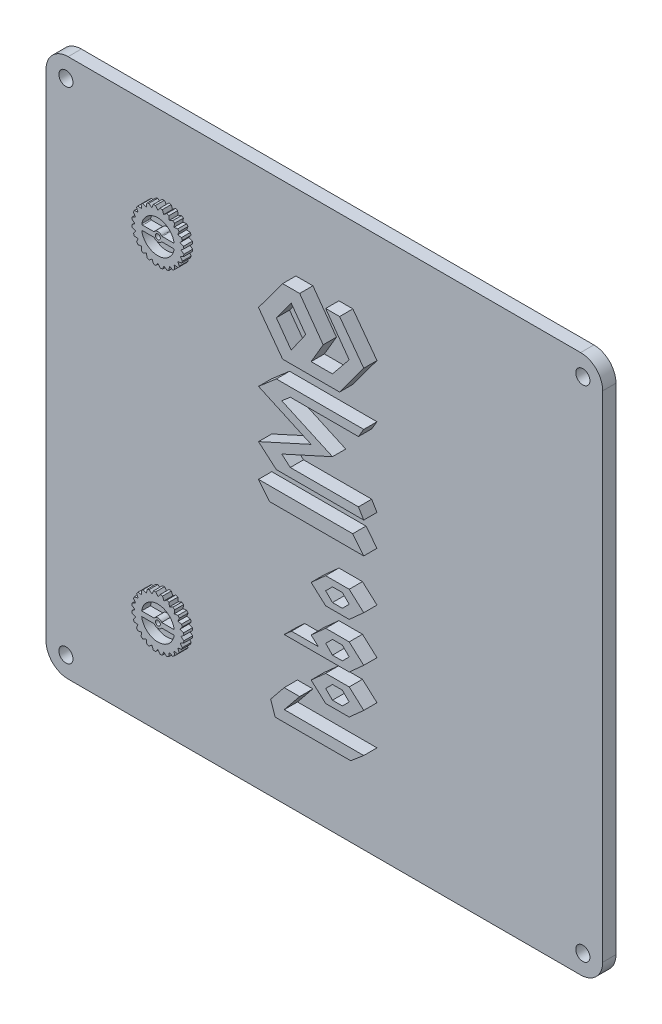
SolidWorks part; units mm, degrees
ref_plane "Front Plane" through (0, 0, 0) normal (0, 0, 1) x (1, 0, 0)
ref_plane "Top Plane" through (0, 0, 0) normal (0, 1, 0) x (1, 0, 0)
ref_plane "Right Plane" through (0, 0, 0) normal (1, 0, 0) x (0, 0, -1)
sketch "Sketch1" plane through (0, 0, 0) normal (0, 0, 1) x (1, 0, 0)
  line L1 (63, 61) -> (-63, 61)
  line L2 (63, 61) -> (63, -61)
  line L3 (63, -61) -> (-63, -61)
  line L4 (-63, 61) -> (-63, -61)
  line L5 (63, 61) -> (-63, -61) construction
  line L6 (63, -61) -> (-63, 61) construction
  point P0 (0, 0)
  dimension "D1" = 126
  dimension "D2" = 122
extrude "Boss-Extrude1" add sketch "Sketch1" along normal blind 3
sketch "Esboço8" plane through (0, 0, 3) normal (0, 0, 1) x (1, 0, 0)
  line L9 (-8.1446, -42.0239) -> (8.9552, -42.0239)
  line L15 (-6.0773, -39.5239) -> (-2.5948, -35.2227)
  line L36 (3.2914, 43.791) -> (6.4479, 43.791)
  line L47 (11.9079, -39.5239) -> (-6.0773, -39.5239)
  line L51 (11.9079, -30.6806) -> (8.6165, -27.7268)
  line L52 (3.2914, -27.7268) -> (0, -30.6806)
  line L53 (0, -30.6806) -> (3.2914, -33.6344)
  line L54 (8.6165, -33.6344) -> (11.9079, -30.6806)
  line L55 (0, -30.6806) -> (11.9079, -30.6806) construction
  line L56 (4.8336, -32.2228) -> (3.2914, -30.6806)
  line L57 (3.2914, -30.6806) -> (4.8336, -29.1384)
  line L58 (7.0744, -29.1384) -> (8.6165, -30.6806)
  line L59 (8.6165, -30.6806) -> (7.0744, -32.2228)
  line L68 (3.2914, -27.7268) -> (8.6165, -27.7268)
  line L69 (3.2914, -33.6344) -> (8.6165, -33.6344)
  line L70 (4.8336, -29.1384) -> (7.0744, -29.1384)
  line L71 (4.8336, -32.2228) -> (7.0744, -32.2228)
  line L72 (3.2914, -24.8048) -> (8.6165, -24.8048)
  line L73 (11.9079, -21.851) -> (8.6165, -24.8048)
  line L74 (8.6165, -18.8972) -> (11.9079, -21.851)
  line L75 (3.2914, -18.8972) -> (8.6165, -18.8972)
  line L76 (0, -21.851) -> (3.2914, -18.8972)
  line L77 (1.6457, -23.3279) -> (0, -21.851)
  line L78 (4.8336, -23.3932) -> (7.0744, -23.3932)
  line L79 (7.0744, -23.3932) -> (8.6165, -21.851)
  line L80 (8.6165, -21.851) -> (7.0744, -20.3088)
  line L81 (4.8336, -20.3088) -> (7.0744, -20.3088)
  line L82 (4.8336, -20.3088) -> (3.2914, -21.851)
  line L83 (3.2914, -21.851) -> (4.8336, -23.3932)
  line L84 (3.2914, -24.8048) -> (-6.0773, -24.8048)
  line L85 (-6.0773, -24.8048) -> (-4.4316, -23.3279)
  line L86 (-4.4316, -23.3279) -> (1.6457, -23.3279)
  line L87 (-2.5948, -35.2227) -> (-6.0948, -35.2227)
  line L94 (3.2914, -14.4937) -> (8.6165, -14.4937)
  line L95 (8.6165, -14.4937) -> (11.9079, -11.5399)
  line L96 (11.9079, -11.5399) -> (8.6165, -8.5862)
  line L97 (3.2914, -8.5862) -> (8.6165, -8.5862)
  line L98 (3.2914, -8.5862) -> (0, -11.5399)
  line L99 (0, -11.5399) -> (3.2914, -14.4937)
  line L100 (8.6165, -11.5399) -> (7.0744, -13.0821)
  line L101 (7.0744, -9.9978) -> (8.6165, -11.5399)
  line L102 (4.8336, -9.9978) -> (7.0744, -9.9978)
  line L103 (3.2914, -11.5399) -> (4.8336, -9.9978)
  line L104 (4.8336, -13.0821) -> (3.2914, -11.5399)
  line L105 (4.8336, -13.0821) -> (7.0744, -13.0821)
  line L106 (-6.0948, -35.2227) -> (-9.1643, -39.0137)
  line L107 (-9.1643, -39.0137) -> (-8.1446, -42.0239)
  line L108 (11.9079, 6.6223) -> (-7.8765, 6.6223)
  line L109 (9.4156, 2.7015) -> (11.9079, -0.4117)
  line L110 (11.9079, -0.4117) -> (-9.4091, -0.4117)
  line L111 (-9.4091, -0.4117) -> (-11.9079, 2.7015)
  line L112 (-11.9079, 2.7015) -> (9.4156, 2.7015)
  line L113 (-7.8765, 6.6223) -> (-11.9079, 10.097)
  line L114 (-11.9079, 10.097) -> (0, 15.5092)
  line L116 (4.8336, 15.5092) -> (-6.6491, 10.2903)
  line L117 (-6.6491, 10.2903) -> (-4.7138, 8.6223)
  line L118 (-4.7138, 8.6223) -> (10.7124, 8.6223)
  line L119 (10.7124, 8.6223) -> (11.9079, 6.6223)
  line L120 (-11.9079, 36.3884) -> (-6.4479, 28.9858)
  line L121 (10.7124, 22.3961) -> (11.9079, 24.3961)
  line L122 (-4.7138, 22.3961) -> (10.7124, 22.3961)
  line L123 (11.9079, 24.3961) -> (-7.8765, 24.3961)
  line L124 (-6.6491, 20.7281) -> (-4.7138, 22.3961)
  line L125 (-7.8765, 24.3961) -> (-11.9079, 20.9215)
  line L126 (4.8336, 15.5092) -> (-6.6491, 20.7281)
  line L127 (-11.9079, 20.9215) -> (0, 15.5092)
  line L128 (-6.4479, 28.9858) -> (6.4479, 28.9858)
  line L129 (6.4479, 28.9858) -> (11.9079, 36.3884)
  line L130 (6.4479, 43.791) -> (11.9079, 36.3884)
  line L131 (-6.4479, 43.791) -> (-2.5948, 43.791)
  line L132 (-11.9079, 36.3884) -> (-6.4479, 43.791)
  line L133 (4.8215, 31.7256) -> (8.6165, 36.3884)
  line L134 (2.7303, 36.3884) -> (0, 31.7256)
  line L135 (0, 31.7256) -> (4.8215, 31.7256)
  line L136 (8.6165, 36.3884) -> (3.2914, 43.791)
  line L137 (3.2914, 43.791) -> (6.4479, 43.791)
  line L138 (2.7303, 36.3884) -> (-2.5948, 43.791)
  line L148 (11.9079, -39.5239) -> (8.9552, -42.0239)
  line L151 (-4.5103, 31.7256) -> (-1.2273, 36.3884)
  line L153 (-1.2273, 36.3884) -> (-4.5103, 40.9523)
  line L154 (-4.5103, 40.9523) -> (-7.8765, 36.3884)
  line L155 (-7.8765, 36.3884) -> (-4.5103, 31.7256)
  point P89 (10.2622, -13.0168)
  dimension "D3" = 3.5
  dimension "D5" = 2
  dimension "D6" = 2
extrude "Ressalto-extrusão3" add sketch "Esboço8" along normal blind 3 contours L148 L47 L15 L87 L106 L107 L9 | L52 L55 L57 L70 L58 L51 L68 | L55 L53 L69 L54 L59 L71 L56 | L86 L85 L84 L72 L73 L74 L75 L76 L77 L83 L82 L81 L80 L79 L78 | L98 L99 L94 L95 L96 L97 L105 L104 L103 L102 L101 L100 | L112 L111 L110 L109 | L125 L127 L114 L113 L108 L119 L118 L117 L116 L126 L124 L122 L121 L123 | L134 L138 L131 L132 L120 L128 L129 L130 L36 L136 L133 L135 L155 L154 L153 L151 region at (-0.7235, -39.9252, 3) region at (-0.5462, 35.7857, 3) region at (10.2622, -30.5579, 3) region at (10.1803, -32.0662, 3) region at (-1.393, -24.6155, 3) region at (1.7345, -12.9179, 3) region at (2.0157, 6.9195, 3) region at (0.0016, 1.145, 3)
sketch "Esboço10" plane through (0, 0, 3) normal (0, 0, 1) x (1, 0, 0)
  line L2 (-30.6628, 39.2244) -> (-29.8737, 38.9014)
  line L3 (-29.8737, 38.9014) -> (-29.8057, 38.4014)
  line L4 (-29.8057, 38.4014) -> (-30.4799, 37.8795)
  line L5 (-30.4799, 37.8795) -> (-29.8057, 37.9207) construction
  line L6 (-30.1466, 39.903) -> (-30.6628, 39.2244)
  line L7 (-31.1874, 40.4761) -> (-30.3417, 40.3684)
  line L8 (-30.3417, 40.3684) -> (-30.1466, 39.903)
  line L9 (-30.8645, 41.2652) -> (-31.1874, 40.4761)
  line L10 (-32.0182, 41.5494) -> (-31.1734, 41.6642)
  line L11 (-31.1734, 41.6642) -> (-30.8645, 41.2652)
  line L12 (-31.9105, 42.3951) -> (-32.0182, 41.5494)
  line L13 (-33.0984, 42.371) -> (-32.3121, 42.7006)
  line L14 (-32.3121, 42.7006) -> (-31.9105, 42.3951)
  line L15 (-33.2133, 43.2159) -> (-33.0984, 42.371)
  line L16 (-34.3545, 42.8851) -> (-33.6803, 43.407)
  line L17 (-33.6803, 43.407) -> (-33.2133, 43.2159)
  line L18 (-34.6841, 43.6714) -> (-34.3545, 42.8851)
  line L19 (-35.7009, 43.0566) -> (-35.1847, 43.7352)
  line L20 (-35.1847, 43.7352) -> (-34.6841, 43.6714)
  line L21 (-36.2228, 43.7308) -> (-35.7009, 43.0566)
  line L22 (-37.0457, 42.8737) -> (-36.7228, 43.6628)
  line L23 (-36.7228, 43.6628) -> (-36.2228, 43.7308)
  line L24 (-37.7243, 43.3899) -> (-37.0457, 42.8737)
  line L25 (-38.2974, 42.3491) -> (-38.1897, 43.1948)
  line L26 (-38.1897, 43.1948) -> (-37.7243, 43.3899)
  line L27 (-39.0865, 42.672) -> (-38.2974, 42.3491)
  line L28 (-39.3707, 41.5183) -> (-39.4855, 42.3631)
  line L29 (-39.4855, 42.3631) -> (-39.0865, 42.672)
  line L30 (-40.2165, 41.626) -> (-39.3707, 41.5183)
  line L31 (-40.1924, 40.4381) -> (-40.522, 41.2244)
  line L32 (-40.522, 41.2244) -> (-40.2165, 41.626)
  line L33 (-41.0372, 40.3232) -> (-40.1924, 40.4381)
  line L34 (-40.7064, 39.182) -> (-41.2283, 39.8562)
  line L35 (-41.2283, 39.8562) -> (-41.0372, 40.3232)
  line L36 (-41.4928, 38.8524) -> (-40.7064, 39.182)
  line L37 (-40.8779, 37.8356) -> (-41.5565, 38.3518)
  line L38 (-41.5565, 38.3518) -> (-41.4928, 38.8524)
  line L39 (-41.5521, 37.3137) -> (-40.8779, 37.8356)
  line L40 (-40.6951, 36.4908) -> (-41.4842, 36.8137)
  line L41 (-41.4842, 36.8137) -> (-41.5521, 37.3137)
  line L42 (-41.2112, 35.8122) -> (-40.6951, 36.4908)
  line L43 (-40.1704, 35.2391) -> (-41.0162, 35.3468)
  line L44 (-41.0162, 35.3468) -> (-41.2112, 35.8122)
  line L45 (-40.4933, 34.45) -> (-40.1704, 35.2391)
  line L46 (-39.3396, 34.1658) -> (-40.1845, 34.051)
  line L47 (-40.1845, 34.051) -> (-40.4933, 34.45)
  line L48 (-39.4473, 33.32) -> (-39.3396, 34.1658)
  line L49 (-38.2594, 33.3442) -> (-39.0457, 33.0145)
  line L50 (-39.0457, 33.0145) -> (-39.4473, 33.32)
  line L51 (-38.1445, 32.4993) -> (-38.2594, 33.3442)
  line L52 (-37.0033, 32.8301) -> (-37.6775, 32.3082)
  line L53 (-37.6775, 32.3082) -> (-38.1445, 32.4993)
  line L54 (-36.6737, 32.0437) -> (-37.0033, 32.8301)
  line L55 (-35.657, 32.6586) -> (-36.1731, 31.98)
  line L56 (-36.1731, 31.98) -> (-36.6737, 32.0437)
  line L57 (-35.1351, 31.9844) -> (-35.657, 32.6586)
  line L58 (-34.3121, 32.8414) -> (-34.6351, 32.0523)
  line L59 (-34.6351, 32.0523) -> (-35.1351, 31.9844)
  line L60 (-33.6335, 32.3253) -> (-34.3121, 32.8414)
  line L61 (-33.0604, 33.3661) -> (-33.1681, 32.5203)
  line L62 (-33.1681, 32.5203) -> (-33.6335, 32.3253)
  line L63 (-32.2713, 33.0432) -> (-33.0604, 33.3661)
  line L64 (-31.9872, 34.1969) -> (-31.8723, 33.352)
  line L65 (-31.8723, 33.352) -> (-32.2713, 33.0432)
  line L66 (-31.1414, 34.0892) -> (-31.9872, 34.1969)
  line L67 (-31.1655, 35.2771) -> (-30.8359, 34.4908)
  line L68 (-30.8359, 34.4908) -> (-31.1414, 34.0892)
  line L69 (-30.3206, 35.392) -> (-31.1655, 35.2771)
  line L70 (-30.6514, 36.5332) -> (-30.1295, 35.859)
  line L71 (-30.1295, 35.859) -> (-30.3206, 35.392)
  line L72 (-29.8651, 36.8628) -> (-30.6514, 36.5332)
  line L73 (-30.4799, 37.8795) -> (-29.8013, 37.3634)
  line L74 (-29.8013, 37.3634) -> (-29.8651, 36.8628)
  line L77 (-34.8245, 38.4014) -> (-31.9963, 38.4014)
  line L78 (-31.9963, 38.4014) -> (-34.8245, 38.4014)
  line L79 (-36.5333, 38.4014) -> (-39.3615, 38.4014)
  line L80 (-36.5333, 37.3137) -> (-39.3615, 37.3137)
  line L81 (-34.8245, 37.3137) -> (-31.9963, 37.3137)
  circle A0 centre (-35.6789, 37.8576) radius 3.7225
  circle A2 centre (-35.6789, 37.8576) radius 1.0128
  circle A3 centre (-35.6789, 37.8576) radius 0.5545
  point P13 (-30.6628, 39.2244)
  point P14 (-30.4799, 37.8795)
  point P109 (-35.6789, 37.8576)
  dimension "D1" = 120
  dimension "D2" = 120
  dimension "D3" = 0.5
  dimension "D4" = 24
extrude "Ressalto-extrusão4" add sketch "Esboço10" along normal blind 2 contours L74 L73 L4 L3 L2 L6 L8 L7 L9 L11 L10 L12 L14 L13 L15 L17 L16 L18 L20 L19 L21 L23 L22 L24 L26 L25 L27 L29 L28 L30 L32 L31 L33 L35 L34 L36 L38 L37 L39 L41 L40 L42 L44 L43 L45 L47 L46 L48 L50 L49 L51 | A2 L81 A0 L77 | A2 L79 A0 L80 | A2 A3 region at (-30.3312, 38.9091, 3) region at (-33.3438, 37.8576, 3) region at (-34.734, 38.1328, 3) region at (-38.0141, 37.8576, 3)
fillet "Filete8" radius 0.2 4 edges at (-39.3615, 38.4014, 4) (-39.3615, 37.3137, 4) (-31.9963, 37.3137, 4) (-31.9963, 38.4014, 4)
fillet "Filete9" radius 0.2 4 edges at (-34.8245, 37.3137, 4) (-36.5333, 37.3137, 4) (-36.5333, 38.4014, 4) (-34.8245, 38.4014, 4)
sketch "Sketch2" plane through (0, 0, 3) normal (0, 0, 1) x (1, 0, 0)
  line L0 (-63, 61) -> (-63, -61) construction
  line L3 (-63, -61) -> (63, -61) construction
  circle A0 centre (-58.5, -56.5) radius 1.6
  point P6 (-58.9171, -61)
  point P7 (-59.5658, -61)
  dimension "D1" = 3.2
  dimension "D3" = 4.5
  dimension "D2" = 4.5
extrude "Cut-Extrude1" cut sketch "Sketch2" against normal up to surface (3 mm away) up to face at (0, 0, 0)
pattern_linear "LPattern1" count 2 spacing 113 along (0, 1, 0) count 2 spacing 117 along (1, 0, 0) of "Cut-Extrude1"
fillet "Fillet1" radius 5 4 edges at (-63, 61, 1.5) (63, 61, 1.5) (63, -61, 1.5) (-63, -61, 1.5)
mirror "Mirror1" about plane through (0, 0, 0) normal (0, 1, 0) of "Ressalto-extrusão4"
sketch "Sketch3" plane through (0, 0, 0) normal (0, 0, -1) x (-1, 0, 0)
  line L0 (-58.835, 51.3559) -> (-58.835, -7.5812) construction
  text T0 "Fran\r\n" font "Bauhaus 93" height 10
extrude "Cut-Extrude2" cut sketch "Sketch3" against normal offset from surface (2 mm away) 1 up to face at (60.1, 56.5, 3)
